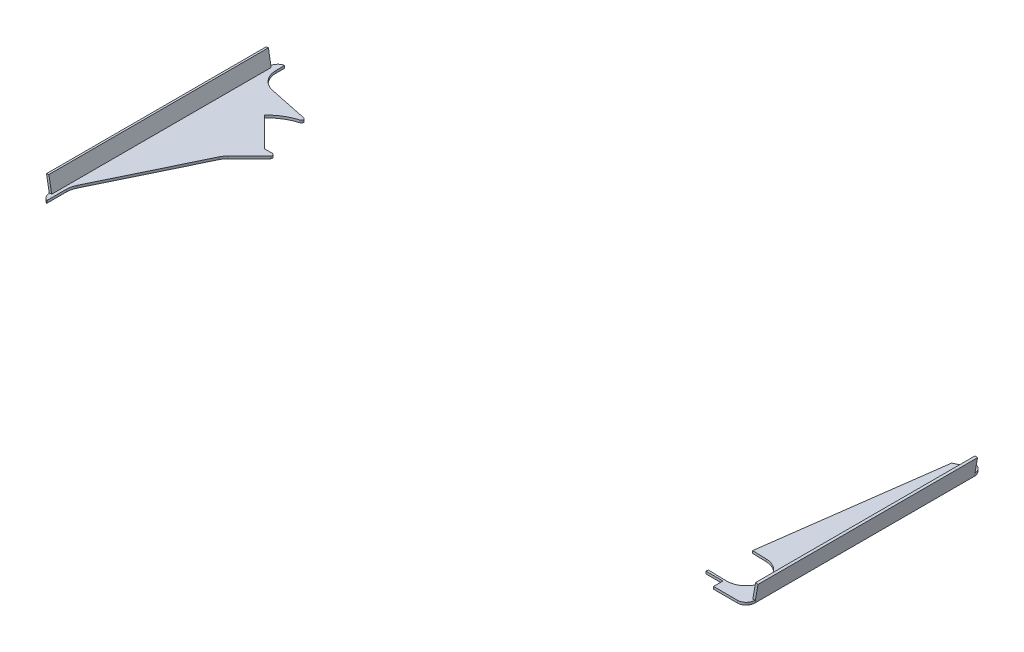
SolidWorks part; units mm, degrees
material "Silicon Rubber"
ref_plane "Front Plane" through (0, 0, 0) normal (0, 0, 1) x (1, 0, 0)
ref_plane "Top Plane" through (0, 0, 0) normal (0, 1, 0) x (1, 0, 0)
ref_plane "Right Plane" through (0, 0, 0) normal (1, 0, 0) x (0, 0, -1)
ref_axis "Axis1" through (0, -55, 0) along (0, 1, 0)
sketch "Sketch1" plane through (0, 0, 0) normal (0, 1, 0) x (1, 0, 0)
  line L4 (-895.35, -308.4859) -> (895.35, -308.4859)
  line L5 (918.0859, -285.75) -> (918.0859, 285.75)
  line L6 (895.35, 308.4859) -> (-895.35, 308.4859)
  line L7 (-918.0859, 285.75) -> (-918.0859, -285.75)
  line L9 (918.0859, -285.75) -> (918.0859, 285.75)
  line L11 (-918.0859, 285.75) -> (-918.0859, -285.75)
  line L12 (789.4601, -278.0497) -> (836.8117, -279.3451)
  line L13 (839.5874, -177.8548) -> (803.1489, -176.8586)
  line L14 (803.1489, -176.8586) -> (864.87, 279.4)
  line L15 (895.35, -308.4859) -> (833.12, -308.4859)
  line L16 (-895.35, -308.4859) -> (895.35, -308.4859) construction
  line L17 (895.35, 308.4859) -> (885.19, 308.4859)
  line L20 (-737.6837, 93.8203) -> (-717.685, 93.8203)
  line L21 (-737.6837, 93.8203) -> (-813.9802, 170.1168)
  line L22 (-737.6837, 93.8203) -> (-813.9802, 170.1168)
  line L26 (885.19, 289.56) -> (885.19, 304.8)
  line L27 (864.87, 279.4) -> (885.19, 289.56)
  line L28 (788.67, -283.89) -> (864.87, 279.4)
  line L29 (833.12, -283.89) -> (788.67, -283.89)
  line L30 (833.12, -304.8) -> (833.12, -283.89)
  line L31 (-889, -304.8) -> (833.12, -304.8)
  line L32 (-904.9131, -255.27) -> (-904.9131, -299.1973)
  line L33 (-779.1931, 16.2516) -> (-899.8431, -233.1475)
  line L34 (-629.3043, 170.1299) -> (-769.3841, 30.0501)
  line L35 (-859.3979, 236.0165) -> (-723.9921, 207.8241)
  line L36 (-899.8431, 302.3693) -> (-899.8431, 285.75)
  line L37 (885.19, 304.8) -> (-889, 304.8)
  line L38 (885.19, 289.56) -> (885.19, 308.4859)
  line L39 (864.87, 279.4) -> (885.19, 289.56)
  line L40 (788.67, -283.89) -> (789.4601, -278.0497)
  line L41 (833.12, -283.89) -> (788.67, -283.89)
  line L42 (833.12, -308.4859) -> (833.12, -283.89)
  line L44 (-904.9131, -255.27) -> (-904.9131, -306.3769)
  line L45 (-779.1931, 16.2516) -> (-899.8431, -233.1475)
  line L46 (-714.1494, 85.2848) -> (-769.3841, 30.0501)
  line L47 (-859.3979, 236.0165) -> (-757.047, 214.7064)
  line L48 (-899.8431, 308.0375) -> (-899.8431, 285.75)
  arc A1 (836.8117, -279.3451) -> (839.5874, -177.8548) centre (838.2, -228.6) ccw construction
  arc A2 (836.8117, -279.3451) -> (839.5874, -177.8548) centre (838.2, -228.6) ccw
  arc A4 (-717.685, 93.8203) -> (-714.1494, 85.2848) centre (-717.685, 88.8203) cw
  arc A5 (895.35, -308.4859) -> (918.0859, -285.75) centre (895.35, -285.75) ccw
  arc A6 (918.0859, 285.75) -> (895.35, 308.4859) centre (895.35, 285.75) ccw
  arc A7 (-895.35, 308.4859) -> (-918.0859, 285.75) centre (-895.35, 285.75) ccw
  arc A8 (-918.0859, -285.75) -> (-895.35, -308.4859) centre (-895.35, -285.75) ccw
  arc A9 (895.35, -308.4859) -> (918.0859, -285.75) centre (895.35, -285.75) ccw
  arc A10 (918.0859, 285.75) -> (895.35, 308.4859) centre (895.35, 285.75) ccw
  arc A11 (-899.8431, 308.0375) -> (-918.0859, 285.75) centre (-895.35, 285.75) ccw
  arc A12 (-918.0859, -285.75) -> (-904.9131, -306.3769) centre (-895.35, -285.75) ccw
  arc A13 (-631.8224, 177.4633) -> (-813.9802, 170.1168) centre (-719.0679, 78.74) ccw
  arc A14 (-756.6403, 205.019) -> (-813.9802, 170.1168) centre (-719.0679, 78.74) ccw
  arc A15 (-756.6403, 205.019) -> (-757.047, 214.7064) centre (-758.0662, 209.8113) ccw
  arc A18 (-904.9131, -299.1973) -> (-889, -304.8) centre (-889, -279.4) ccw
  arc A19 (-899.8431, -233.1475) -> (-904.9131, -255.27) centre (-854.1131, -255.27) ccw
  arc A20 (-769.3841, 30.0501) -> (-779.1931, 16.2516) centre (-733.4631, -5.8709) ccw
  arc A21 (-629.3043, 170.1299) -> (-715.1793, 206.781) centre (-719.0679, 78.74) ccw
  arc A22 (-723.9921, 207.8241) -> (-715.1793, 206.781) centre (-713.6372, 257.5576) ccw
  arc A23 (-899.8431, 285.75) -> (-859.3979, 236.0165) centre (-849.0431, 285.75) ccw
  arc A24 (-889, 304.8) -> (-899.8431, 302.3693) centre (-889, 279.4) ccw
  arc A26 (-899.8431, -233.1475) -> (-904.9131, -255.27) centre (-854.1131, -255.27) ccw
  arc A27 (-769.3841, 30.0501) -> (-779.1931, 16.2516) centre (-733.4631, -5.8709) ccw
  arc A30 (-899.8431, 285.75) -> (-859.3979, 236.0165) centre (-849.0431, 285.75) ccw
  dimension "D1" = 0
  dimension "D4" = 5
  dimension "D3" = 10
  dimension "D2" = 0
extrude "Boss-Extrude1" add sketch "Sketch1" along normal blind 6.35
ref_plane "Plane1" through (-890.4022, -157.0019, 0) normal (0.9848, 0.1736, 0) x (0, 0, -1)
ref_plane "Plane2" through (-890.4022, -157.0019, 0) normal (0.9848, 0.1736, 0) x (0, 0, -1)
sketch "Sketch2" plane through (-890.4022, -157.0019, 0) normal (0.9848, 0.1736, 0) x (0, 0, -1)
  line L4 (285.75, 159.4239) -> (285.75, 206.2122)
  line L5 (285.75, 206.2122) -> (-285.75, 206.2122)
  line L6 (-285.75, 206.2122) -> (-285.75, 159.4239)
  line L7 (-285.75, 159.4239) -> (285.75, 159.4239)
  line L8 (285.75, 159.4239) -> (285.75, 206.2122)
  line L9 (285.75, 206.2122) -> (-285.75, 206.2122)
  line L10 (-285.75, 206.2122) -> (-285.75, 159.4239)
  line L11 (-285.75, 159.4239) -> (285.75, 159.4239)
  dimension "D1" = 0
extrude "Boss-Extrude2" add sketch "Sketch2" along normal blind 6.35
ref_plane "Plane3" through (890.4022, -157.0019, 0) normal (-0.9848, 0.1736, 0) x (0, 0, 1)
sketch "Sketch3" plane through (890.4022, -157.0019, 0) normal (-0.9848, 0.1736, 0) x (0, 0, 1)
  line L4 (285.75, 159.4239) -> (285.75, 206.2122)
  line L5 (285.75, 206.2122) -> (-285.75, 206.2122)
  line L6 (-285.75, 206.2122) -> (-285.75, 159.4239)
  line L7 (-285.75, 159.4239) -> (285.75, 159.4239)
  line L8 (285.75, 159.4239) -> (285.75, 206.2122)
  line L9 (285.75, 206.2122) -> (-285.75, 206.2122)
  line L10 (-285.75, 206.2122) -> (-285.75, 159.4239)
  line L11 (-285.75, 159.4239) -> (285.75, 159.4239)
  dimension "D1" = 0
extrude "Boss-Extrude3" add sketch "Sketch3" along normal blind 6.35
